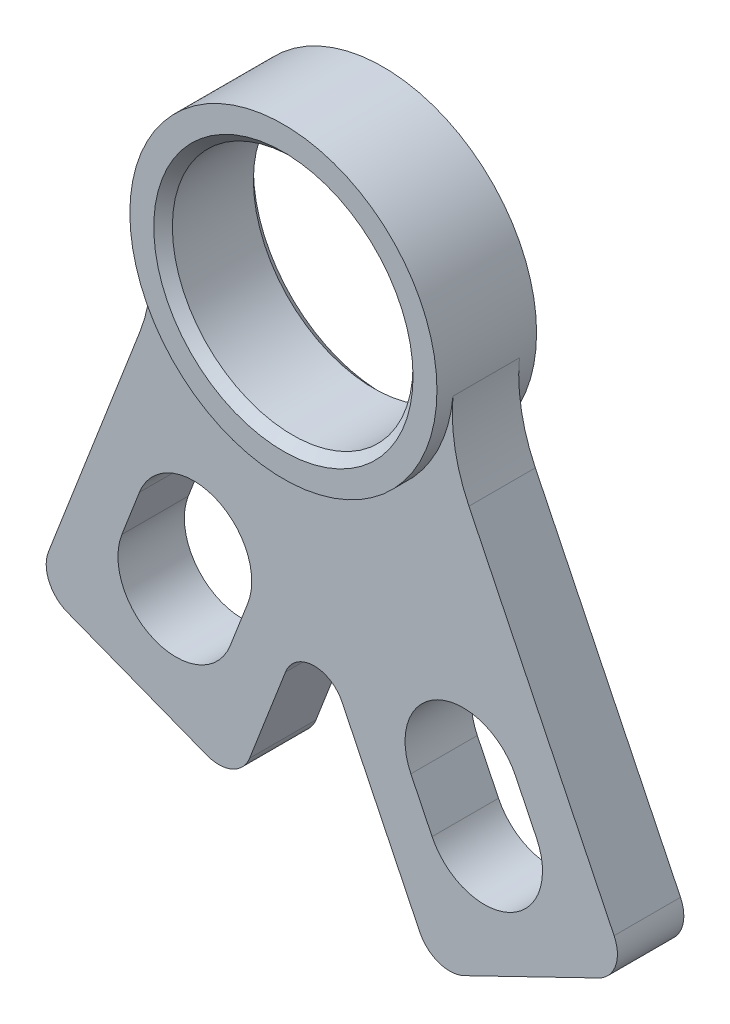
SolidWorks part; units mm, degrees
material "AISI 4130 Steel, annealed at 865C"
ref_plane "X-Y Datum" through (0, 0, 0) normal (0, 0, 1) x (1, 0, 0)
ref_plane "X-Z Datum" through (0, 0, 0) normal (0, 1, 0) x (1, 0, 0)
ref_plane "Y-Z Datum" through (0, 0, 0) normal (1, 0, 0) x (0, 0, -1)
sketch "Sketch1" plane through (0, 0, 0) normal (0, 0, 1) x (1, 0, 0)
  line L0 (-11.8513, -30.596) -> (-10.1727, -26.2625) construction
  line L1 (-17.0325, -28.5891) -> (-15.3539, -24.2556)
  line L2 (-6.6702, -32.6029) -> (-4.9916, -28.2694)
  line L3 (17.6273, -36.3496) -> (15.5995, -32.168) construction
  line L4 (12.6279, -38.774) -> (10.6001, -34.5924)
  line L5 (22.6267, -33.9252) -> (20.5989, -29.7436)
  line L6 (-15.3053, -10.945) -> (-25.2005, -36.4911)
  line L7 (-25.2005, -36.4911) -> (-5.9563, -43.9453)
  line L10 (12.8452, -50.1367) -> (31.4144, -41.1318)
  line L11 (31.4144, -41.1318) -> (16.1501, -9.655)
  line L12 (-101.5262, -262.1058) -> (0, 0) construction
  line L13 (-5.9563, -43.9453) -> (-1.3899, -32.1564)
  line L14 (-13.8582, -35.7772) -> (-15.5784, -40.2182) construction
  line L15 (20.0517, -41.349) -> (22.1298, -45.6343) construction
  line L16 (21.6128, -31.8344) -> (25.898, -29.7564) construction
  line L17 (-16.1932, -26.4223) -> (-20.6341, -24.7021) construction
  line L18 (-16.0677, -12.9132) -> (3.1765, -20.3674) construction
  line L19 (3.1765, -20.3674) -> (-5.9563, -43.9453) construction
  line L20 (-5.8309, -30.4362) -> (-1.3899, -32.1564) construction
  line L21 (-8.1658, -21.0813) -> (-6.4456, -16.6403) construction
  line L22 (12.8452, -50.1367) -> (1.8124, -27.3859) construction
  line L23 (1.8124, -27.3859) -> (20.3817, -18.3809) construction
  line L24 (11.614, -36.6832) -> (7.3288, -38.7613) construction
  line L25 (13.1751, -27.1686) -> (11.097, -22.8834) construction
  line L29 (11.4598, -47.2799) -> (4.0182, -31.9346)
  line L30 (0, 0) -> (127.0738, -262.0414) construction
  circle A0 centre (0, 0) radius 11.5062
  arc A1 (-17.0325, -28.5891) -> (-6.6702, -32.6029) centre (-11.8513, -30.596) ccw
  arc A2 (-4.9916, -28.2694) -> (-15.3539, -24.2556) centre (-10.1727, -26.2625) ccw
  arc A3 (12.6279, -38.774) -> (22.6267, -33.9252) centre (17.6273, -36.3496) ccw
  arc A4 (20.5989, -29.7436) -> (10.6001, -34.5924) centre (15.5995, -32.168) ccw
  arc A5 (14.6226, -1.3108) -> (-14.4661, -2.5037) centre (0, 0) ccw
  arc A6 (16.1501, -9.655) -> (14.6226, -1.3108) centre (30.4342, -2.7281) cw
  arc A7 (-15.3053, -10.945) -> (-14.4661, -2.5037) centre (-30.1086, -5.211) ccw
  arc A10 (15.702, -48.7513) -> (11.4598, -47.2799) centre (14.3166, -45.8945) cw
  circle A12 centre (14.3166, -45.8945) radius 3.175 construction
  arc A14 (-14.4661, -2.5037) -> (14.6226, -1.3108) centre (0, 0) ccw
  arc A15 (-1.3899, -32.1564) -> (4.0182, -31.9346) centre (1.3624, -33.2225) cw
  arc A16 (-4.8201, -41.0121) -> (-8.9441, -42.7879) centre (-7.7701, -39.838) cw
  point P5 (-11.012, -28.4293)
  point P11 (16.6134, -34.2588)
  point P24 (22.1298, -45.6343)
  point P39 (20.0517, -41.349)
  dimension "D1" = 23.0124
  dimension "D2" = 3.175
  dimension "D8" = 15.875
  dimension "D9" = 3.175
  dimension "D6" = 3.175
  dimension "D7" = 17.4334
  dimension "D3" = 20.6375
  dimension "D4" = 4.7625
  dimension "D5" = 25.2848
  dimension "D10" = 9.4968
extrude "Boss-Extrude2" add sketch "Sketch1" along normal mid plane 9.525 contours A5 A14 A0 region at (-0.5846, 14.254, 0)
extrude "Boss-Extrude3" add sketch "Sketch1<4>" along normal mid plane 6.35 contours A14 A7 L6 L7 A10 L10 L11 A6 A4 L5 A3 L4 A2 L2 A1 L1 region at (3.4881, -27.0227, 0)
sketch "Sketch1<4>" plane through (0, 0, 0) normal (0, 0, 1) x (1, 0, 0) same geometry as "Sketch1"
fillet "Fillet1" radius 3.175 2 edges at (-25.2005, -36.4911, 0) (31.4144, -41.1318, 0)
chamfer "Chamfer1" distance 0.889 angle 45 2 edges at (11.5062, 0, -4.7625) (11.5062, 0, 4.7625)
fillet "Fillet2" [suppressed] radius 1.27
